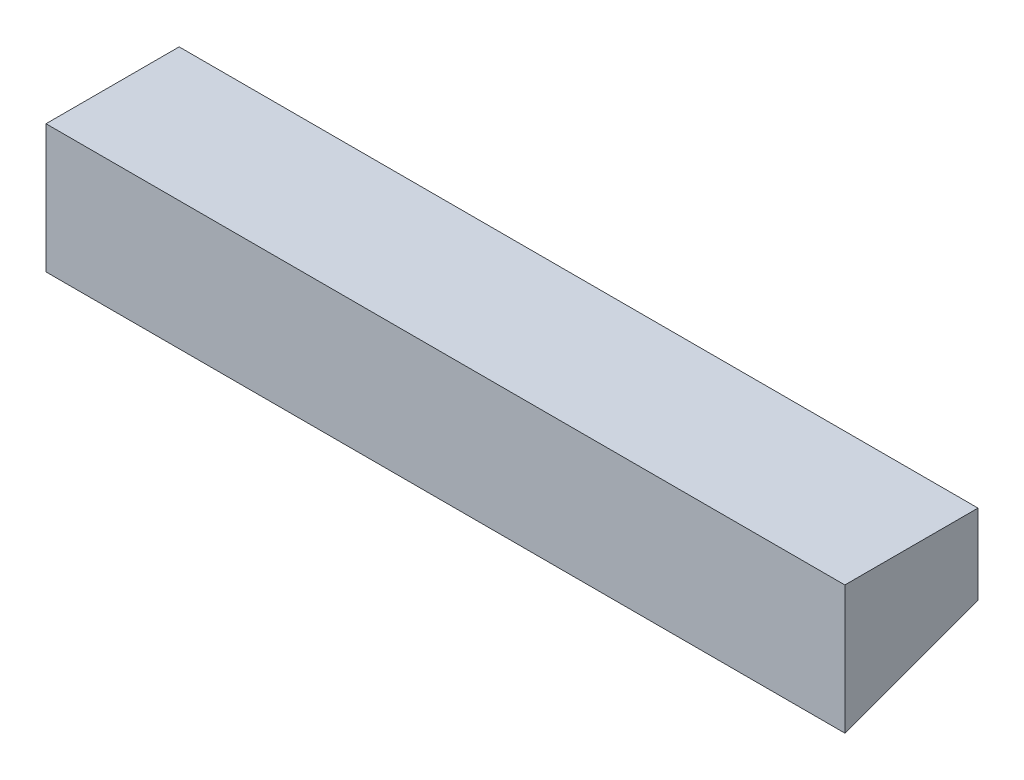
SolidWorks part; units mm, degrees
material "AISI 304"
ref_plane "Спереди" through (0, 0, 0) normal (0, 0, 1) x (1, 0, 0)
ref_plane "Сверху" through (0, 0, 0) normal (0, 1, 0) x (1, 0, 0)
ref_plane "Справа" through (0, 0, 0) normal (1, 0, 0) x (0, 0, -1)
sketch "Эскиз1" plane through (0, 0, 0) normal (0, 0, 1) x (1, 0, 0)
  line L0 (0, 2.5) -> (0, -2.5) construction
  line L1 (-15, 0) -> (15, 0) construction
  line L3 (-15, 2.5) -> (15, 2.5)
  line L4 (-15, 2.5) -> (-15, -2.5)
  line L5 (-15, -2.5) -> (15, -2.5)
  line L6 (15, 2.5) -> (15, -2.5)
  point P9 (-25, 22.5722)
  dimension "D1" = 30
  dimension "D2" = 5
extrude "Бобышка-Вытянуть1" add sketch "Эскиз1" along normal mid plane 5
chamfer "Фаска1" distance 2 angle 70 1 edges at (0, -2.5, -2.5) first distance on face at (0, 0, -2.5)
